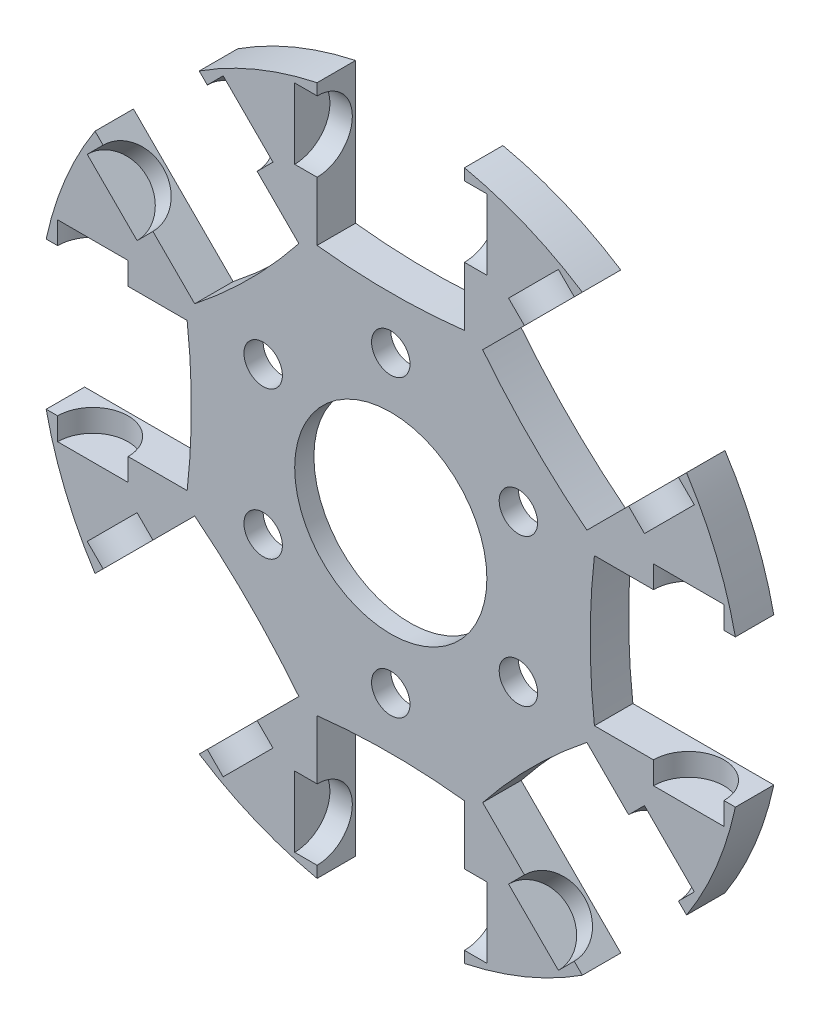
SolidWorks part; units mm, degrees
ref_plane "Front Plane" through (0, 0, 0) normal (0, 0, 1) x (1, 0, 0)
ref_plane "Top Plane" through (0, 0, 0) normal (0, 1, 0) x (1, 0, 0)
ref_plane "Right Plane" through (0, 0, 0) normal (1, 0, 0) x (0, 0, -1)
sketch "Sketch2" plane through (0, 0, 0) normal (0, 0, 1) x (1, 0, 0)
  line L0 (0, -2.3056) -> (0, 37.2834) construction
  line L1 (-5.75, 28.5556) -> (5.75, 28.5556) construction
  line L2 (-5.75, 26.8921) -> (-5.75, 15.8921)
  line L3 (5.75, 26.8921) -> (5.75, 15.8921)
  line L4 (14.9498, 23.0815) -> (7.1716, 15.3033)
  line L5 (23.0815, 14.9498) -> (15.3033, 7.1716)
  line L6 (26.8921, 5.75) -> (15.8921, 5.75)
  line L7 (26.8921, -5.75) -> (15.8921, -5.75)
  line L8 (23.0815, -14.9498) -> (15.3033, -7.1716)
  line L9 (14.9498, -23.0815) -> (7.1716, -15.3033)
  line L10 (5.75, -26.8921) -> (5.75, -15.8921)
  line L11 (-5.75, -26.8921) -> (-5.75, -15.8921)
  line L12 (-14.9498, -23.0815) -> (-7.1716, -15.3033)
  line L13 (-23.0815, -14.9498) -> (-15.3033, -7.1716)
  line L14 (-26.8921, -5.75) -> (-15.8921, -5.75)
  line L15 (-26.8921, 5.75) -> (-15.8921, 5.75)
  line L16 (-23.0815, 14.9498) -> (-15.3033, 7.1716)
  line L17 (-14.9498, 23.0815) -> (-7.1716, 15.3033)
  circle A0 centre (0, 0) radius 27.5
  circle A1 centre (0, 0) radius 11.5 construction
  circle A2 centre (0, 0) radius 14 construction
  circle A3 centre (-9.9593, 5.75) radius 1.5
  circle A4 centre (0, 11.5) radius 1.5
  circle A5 centre (9.9593, 5.75) radius 1.5
  circle A6 centre (9.9593, -5.75) radius 1.5
  circle A7 centre (0, -11.5) radius 1.5
  circle A8 centre (-9.9593, -5.75) radius 1.5
  arc A9 (-5.75, 15.8921) -> (5.75, 15.8921) centre (0, 65.5604) ccw
  arc A10 (7.1716, 15.3033) -> (15.3033, 7.1716) centre (46.3582, 46.3582) ccw
  arc A11 (15.8921, 5.75) -> (15.8921, -5.75) centre (65.5604, 0) ccw
  arc A12 (15.3033, -7.1716) -> (7.1716, -15.3033) centre (46.3582, -46.3582) ccw
  arc A13 (5.75, -15.8921) -> (-5.75, -15.8921) centre (0, -65.5604) ccw
  arc A14 (-7.1716, -15.3033) -> (-15.3033, -7.1716) centre (-46.3582, -46.3582) ccw
  arc A15 (-15.8921, -5.75) -> (-15.8921, 5.75) centre (-65.5604, 0) ccw
  arc A16 (-15.3033, 7.1716) -> (-7.1716, 15.3033) centre (-46.3582, 46.3582) ccw
  circle A19 centre (0, 0) radius 7.5
  circle A20 centre (0, 0) radius 14
  point P9 (0, 28.5556)
  point P25 (0, 0)
  point P67 (1.5089, -0.625)
  point P69 (0, 0)
  point P75 (0, 0)
  point P79 (0, 0)
  point P80 (0, 0)
  point P81 (0, 0)
  point P83 (-22.6761, 7.3679)
  point P89 (-16.1374, 5.2433)
  dimension "D1" = 55
  dimension "D2" = 11.5
  dimension "37" = 23
  dimension "D3" = 8
  dimension "35" = 28
  dimension "D4" = 3
  dimension "D8" = 15
  dimension "D7" = 50
  dimension "D6" = 11
  dimension "D5" = 6
extrude "Boss-Extrude2" add sketch "Sketch2" along normal blind 3 contours A0 L3 A9 L2 A20 | A20 A3 A4 A5 A6 A7 A8 A19 region at (-6.5106, 21.3921, 0) region at (-13.604, 0, 0)
extrude "Boss-Extrude3" add sketch "Sketch2<4>" along normal blind 3 contours A20 A8 A1 A3 A4 A5 A6 A7 region at (-13.604, 0, 0)
sketch "Sketch2<4>" plane through (0, 0, 0) normal (0, 0, 1) x (1, 0, 0) same geometry as "Sketch2"
sketch "Sketch3" plane through (0, 0, 3) normal (0, 0, 1) x (1, 0, 0)
  line L0 (0, 28.1882) -> (0, 8.7236) construction
  line L1 (-4.625, 27.1083) -> (4.625, 27.1083) construction
  line L3 (-6.683, 23) -> (6.8867, 23) construction
  line L4 (-7.5, 26) -> (7.5, 26)
  line L5 (7.5, 26) -> (7.5, 23.25)
  line L6 (-7.5, 26) -> (-7.5, 23.25)
  line L7 (7.5, 23.25) -> (-7.5, 23.25)
  point P15 (0, 26)
  dimension "D1" = 23
  dimension "D2" = 15
  dimension "D3" = 3
  dimension "D4" = 2.75
revolve "Cut-Revolve1" cut sketch "Sketch3" angle 360 about L7
sketch "Sketch5" plane through (0, 0, 0) normal (0, 0, -1) x (-1, 0, 0)
  circle A0 centre (0, 0) radius 15.5
  dimension "D1" = 31
extrude "Cut-Extrude2" cut sketch "Sketch5" against normal blind 1.5
pattern_circular "CirPattern2" count 8 over 360 about axis through (0, 0, 3) along (0, 0, 1) of "Cut-Revolve1"
